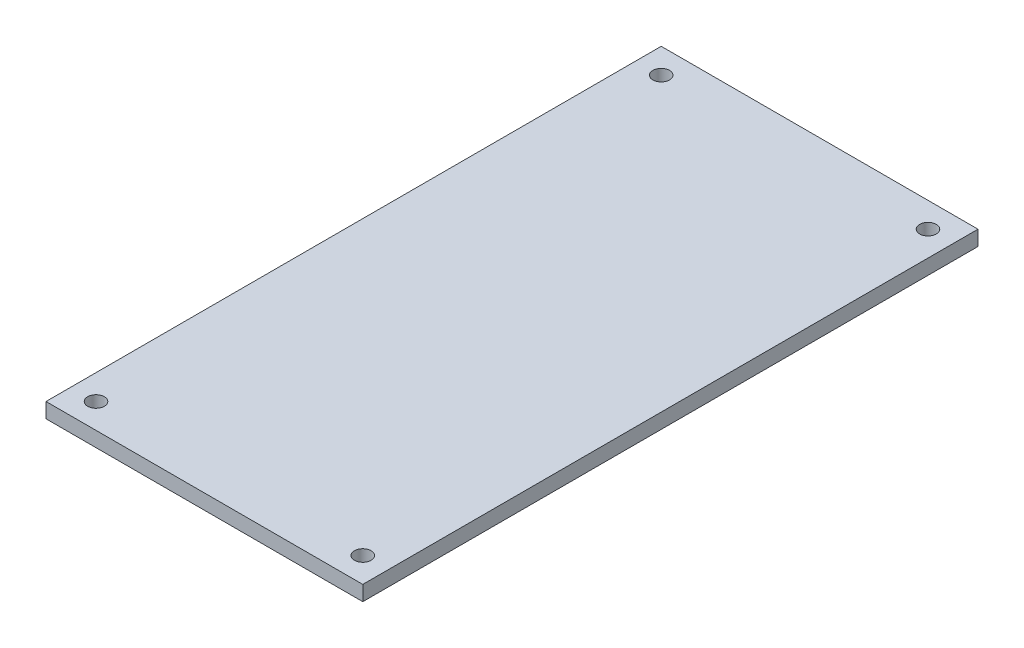
SolidWorks part; units mm, degrees
ref_plane "Front Plane" through (0, 0, 0) normal (0, 0, 1) x (1, 0, 0)
ref_plane "Top Plane" through (0, 0, 0) normal (0, 1, 0) x (1, 0, 0)
ref_plane "Right Plane" through (0, 0, 0) normal (1, 0, 0) x (0, 0, -1)
ref_axis "X-Axis" through (-88.99, 0, 0) along (1, 0, 0)
ref_axis "Y-Axis" through (0, 55, 0) along (0, -1, 0)
ref_axis "Z-Axis" through (0, 0, -88.99) along (0, 0, 1)
sketch "Sketch1" plane through (0, 0, 0) normal (0, 1, 0) x (1, 0, 0)
  line L1 (-19, -36.9) -> (19, -36.9)
  line L2 (-19, -36.9) -> (-19, 36.9)
  line L3 (-19, 36.9) -> (19, 36.9)
  line L4 (19, -36.9) -> (19, 36.9)
  line L5 (-19, -36.9) -> (19, 36.9) construction
  line L6 (-19, 36.9) -> (19, -36.9) construction
  point P0 (0, 0)
  dimension "D1" = 73.8
  dimension "D2" = 38
extrude "Boss-Extrude1" add sketch "Sketch1" along normal blind 1.8
sketch "Sketch2" plane through (0, 1.8, 0) normal (0, 1, 0) x (1, 0, 0)
  line L0 (-19, 33.9) -> (19, 33.9) construction
  line L1 (-19, 36.9) -> (-19, -36.9) construction
  line L2 (19, -36.9) -> (19, 36.9) construction
  line L3 (19, 36.9) -> (-19, 36.9) construction
  circle A0 centre (-16, 33.9) radius 1
  circle A1 centre (16, 33.9) radius 1
  dimension "D2" = 2
  dimension "D1" = 3
  dimension "D3" = 3
  dimension "D4" = 3
extrude "Cut-Extrude1" cut sketch "Sketch2" against normal through all
mirror "Mirror1" about plane through (0, 0, 0) normal (0, 0, 1) of "Cut-Extrude1"
equation "\"D4@Sketch2\"=\"D1@Sketch2\""
